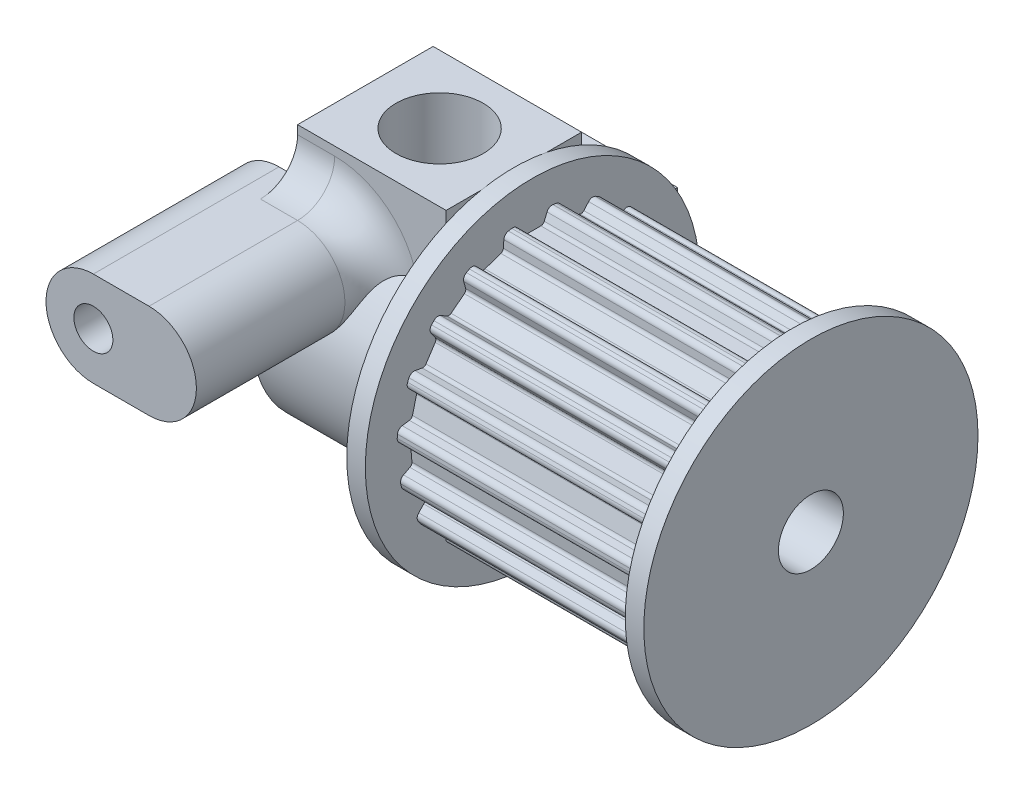
SolidWorks part; units mm, degrees
material "PLA Black"
ref_plane "Front" through (0, 0, 0) normal (0, 0, 1) x (1, 0, 0)
ref_plane "Top" through (0, 0, 0) normal (0, 1, 0) x (1, 0, 0)
ref_plane "Right" through (0, 0, 0) normal (1, 0, 0) x (0, 0, -1)
sketch "Sketch1" plane through (0, 0, 0) normal (1, 0, 0) x (0, 0, -1)
  line L0 (1.118, 1) -> (-1.118, 1) construction
  line L1 (-3.65, 4.8249) -> (3.65, 4.8249)
  line L2 (4.8249, 3.65) -> (4.8249, -3.65)
  line L3 (0, 0) -> (11.6334, 0) construction
  line L4 (0, 0) -> (0, 8.6732) construction
  arc A0 (-1.118, 1) -> (1.118, 1) centre (0, 0) ccw construction
  circle A1 centre (0, 0) radius 1.75
  arc A2 (4.8249, -3.65) -> (-3.65, 4.8249) centre (0, 0) cw
  arc A3 (4.8249, 3.65) -> (3.65, 4.8249) centre (0, 0) ccw
  dimension "D1" = 3
  dimension "D3" = 0.25
  dimension "D5" = 6.05
  dimension "D2" = 1
  dimension "D4" = 7.3
extrude "Boss-Extrude1" add sketch "Sketch1" along normal mid plane 8
sketch "Sketch2" plane through (0, 4.8249, 0) normal (0, 1, 0) x (1, 0, 0)
  circle A0 centre (0, 0) radius 2.35
  dimension "D1" = 4.7
extrude "Cut-Extrude1" cut sketch "Sketch2" against normal blind 5
sketch "Sketch7" plane through (4, 0, 0) normal (1, 0, 0) x (0, 0, -1)
  circle A0 centre (0, 0) radius 1.75 construction
  circle A1 centre (0, 0) radius 7.3
  circle A2 centre (0, 0) radius 1.75
  dimension "D1" = 14.6
extrude "Boss-Extrude5" add sketch "Sketch7" along normal blind 15
sketch "Sketch8" plane through (19, 0, 0) normal (1, 0, 0) x (0, 0, -1)
  line L0 (-0.4541, 6.5499) -> (0.4528, 6.5499)
  line L1 (0.6374, 6.6734) -> (0.7865, 7.0333)
  line L2 (-0.6389, 6.6734) -> (-0.788, 7.0333)
  line L6 (0, 9.2013) -> (0, 0) construction
  arc A0 (0.4528, 6.5499) -> (0.6374, 6.6734) centre (0.4526, 6.7499) ccw
  arc A1 (-0.4541, 6.5499) -> (-0.6389, 6.6734) centre (-0.4541, 6.7499) cw
  arc A2 (0.7865, 7.0333) -> (1.1093, 7.2152) centre (1.0638, 6.9187) cw
  arc A3 (-0.788, 7.0333) -> (-1.1108, 7.215) centre (-1.0652, 6.9185) ccw
  circle A4 centre (0, 0) radius 7.3 construction
  arc A5 (-1.1108, 7.215) -> (1.1093, 7.2152) centre (0, 0) cw
  point P3 (-0.0007, 6.5499)
  point P15 (0, 9.84)
extrude "Cut-Extrude3" cut sketch "Sketch8" against normal up to surface (15 mm away) up to face at (4, 0, -7.3)
pattern_circular "CirPattern1" count 19 over 360 about axis through (19, 0, 0) along (-1, 0, 0) of "Cut-Extrude3"
sketch "Sketch9" plane through (19, 0, 0) normal (1, 0, 0) x (0, 0, -1)
  circle A0 centre (0, 0) radius 9
  circle A1 centre (0, 0) radius 1.75 construction
  circle A2 centre (0, 0) radius 1.75
  dimension "D1" = 18
extrude "Boss-Extrude6" add sketch "Sketch9" along normal blind 1
sketch "Sketch10" plane through (4, 0, 0) normal (-1, 0, 0) x (0, 0, 1)
  circle A0 centre (0, 0) radius 9
  circle A1 centre (0, 0) radius 9 construction
  circle A2 centre (0, 0) radius 1.75 construction
  circle A3 centre (0, 0) radius 1.75
extrude "Boss-Extrude7" add sketch "Sketch10" against normal blind 1
sketch "Sketch3" plane through (0, 0, -4.8249) normal (0, 0, -1) x (-1, 0, 0)
  circle A0 centre (0, 0) radius 2.35
  dimension "D1" = 4.7
extrude "Cut-Extrude2" cut sketch "Sketch3" against normal blind 5
sketch "Sketch4" plane through (0, 4.8249, 0) normal (0, 1, 0) x (1, 0, 0)
  line L0 (4, 3.65) -> (-4, 3.65) construction
  line L2 (4, -3.65) -> (-4, -3.65) construction
  line L3 (-4, 3.65) -> (-4, -3.65) construction
  line L4 (4, 3.65) -> (-4, 3.65)
  line L5 (4, 3.65) -> (4, -3.65)
  line L6 (4, -3.65) -> (-4, -3.65)
  line L7 (-4, 3.65) -> (-4, -3.65)
  line L8 (4, 7.3) -> (4, -7.3) construction
  circle A0 centre (0, 0) radius 2.35 construction
  circle A1 centre (0, 0) radius 2.35
extrude "Boss-Extrude2" add sketch "Sketch4" along normal blind 4
sketch "Sketch5" plane through (0, 0, -4.8249) normal (0, 0, -1) x (-1, 0, 0)
  line L0 (-4, 3.65) -> (4, 3.65) construction
  line L1 (4, -3.65) -> (4, 3.65) construction
  line L2 (-4, -3.65) -> (4, -3.65) construction
  line L4 (-4, 3.65) -> (4, 3.65)
  line L5 (4, -3.65) -> (4, 3.65)
  line L6 (-4, -3.65) -> (4, -3.65)
  line L7 (-4, -3.65) -> (-4, 3.65)
  line L8 (-4, -7.3) -> (-4, 7.3) construction
  circle A0 centre (0, 0) radius 2.35 construction
  circle A1 centre (0, 0) radius 2.35
extrude "Boss-Extrude3" add sketch "Sketch5" along normal blind 4
ref_axis "Axis1" through (20, 0, 0) along (-1, 0, 0)
sketch "Sketch6" plane through (0, 0, 3.65) normal (0, 0, 1) x (1, 0, 0)
  line L0 (-4, 8.8249) -> (-4, 4.8249) construction
  line L2 (-2, 6.3555) -> (-5, 6.3555)
  line L3 (-5, 1.2545) -> (-2, 1.2545)
  line L6 (20, 0) -> (-4, 0) construction
  circle A0 centre (-5, 3.805) radius 1.0505
  arc A1 (-5, 6.3555) -> (-5, 1.2545) centre (-5, 3.805) ccw
  arc A2 (-2, 6.3555) -> (-2, 1.2545) centre (-2, 3.805) cw
  dimension "D1" = 2.101
  dimension "D2" = 3.805
  dimension "D3" = 1.5
  dimension "D4" = 1
  dimension "D5" = 3
extrude "Boss-Extrude4" add sketch "Sketch6" along normal blind 10
fillet "Fillet1" radius 2 2 edges at (-0.6029, 5.9388, 3.65) (-3, 6.3555, 3.65)
equation "\"knee_angle\"= 70"
equation "\"ankle_angle\" = 80"
equation "\"hip_angle\" = 40"
equation "\"spring_ankle_parallel_arm_diameter\"= 1.5"
equation "\"spring_ankle_parallel_arm_length\"= 13"
equation "\"spring_ankle_parallel_intern_diameter\"= 5.7"
equation "\"spring_ankle_parallel_angle\"= \"ankle_angle\""
equation "\"spring_ankle_parallel_turns\"= 3"
equation "\"spring_ankle_parallel_pitch\"= \"spring_ankle_parallel_arm_diameter\" * 1.01"
equation "\"spring_ankle_parallel_cutting_distance\"= (1-\"spring_ankle_parallel_angle\" / 360) * \"spring_ankle_parallel_pitch\""
equation "\"spring_ankle_serial_arm_diameter\"= 1.91"
equation "\"spring_ankle_serial_arm_length\"= 10"
equation "\"spring_ankle_serial_intern_diameter\"= 5.7"
equation "\"spring_ankle_serial_angle\"= \"90\""
equation "\"spring_ankle_serial_turns\"= 3"
equation "\"spring_ankle_serial_pitch\"= \"spring_ankle_serial_arm_diameter\" * 1.01"
equation "\"spring_ankle_serial_cutting_distance\"= (1-\"spring_ankle_serial_angle\" / 360) * \"spring_ankle_serial_pitch\""
equation "\"spring_knee_parallel_arm_diameter\"= 1.5"
equation "\"spring_knee_parallel_arm_length\"= 13"
equation "\"spring_knee_parallel_intern_diameter\"= 5.7"
equation "\"spring_knee_parallel_angle\"= -\"knee_angle\" + 90"
equation "\"spring_knee_parallel_turns\"= 3"
equation "\"spring_knee_parallel_pitch\"= \"spring_knee_parallel_arm_diameter\" * 1.01"
equation "\"spring_knee_parallel_cutting_distance\"= (1-(\"spring_knee_parallel_angle\") / 360) * \"spring_knee_parallel_pitch\""
equation "\"spring_knee_serial_arm_diameter\"= 1.91"
equation "\"spring_knee_serial_arm_length\"= 10"
equation "\"spring_knee_serial_intern_diameter\"= 5.7"
equation "\"spring_knee_serial_angle\"= \"90\""
equation "\"spring_knee_serial_turns\"= 3"
equation "\"spring_knee_serial_pitch\"= \"spring_knee_serial_arm_diameter\" * 1.01"
equation "\"spring_knee_serial_cutting_distance\"= (1-\"spring_knee_serial_angle\" / 360) * \"spring_knee_serial_pitch\""
equation "\"D2@Sketch6\" = ( \"spring_knee_serial_intern_diameter\" + \"spring_knee_serial_arm_diameter\" ) / 2"
equation "\"D1@Sketch6\"=\"spring_knee_serial_arm_diameter\"*1.1"
